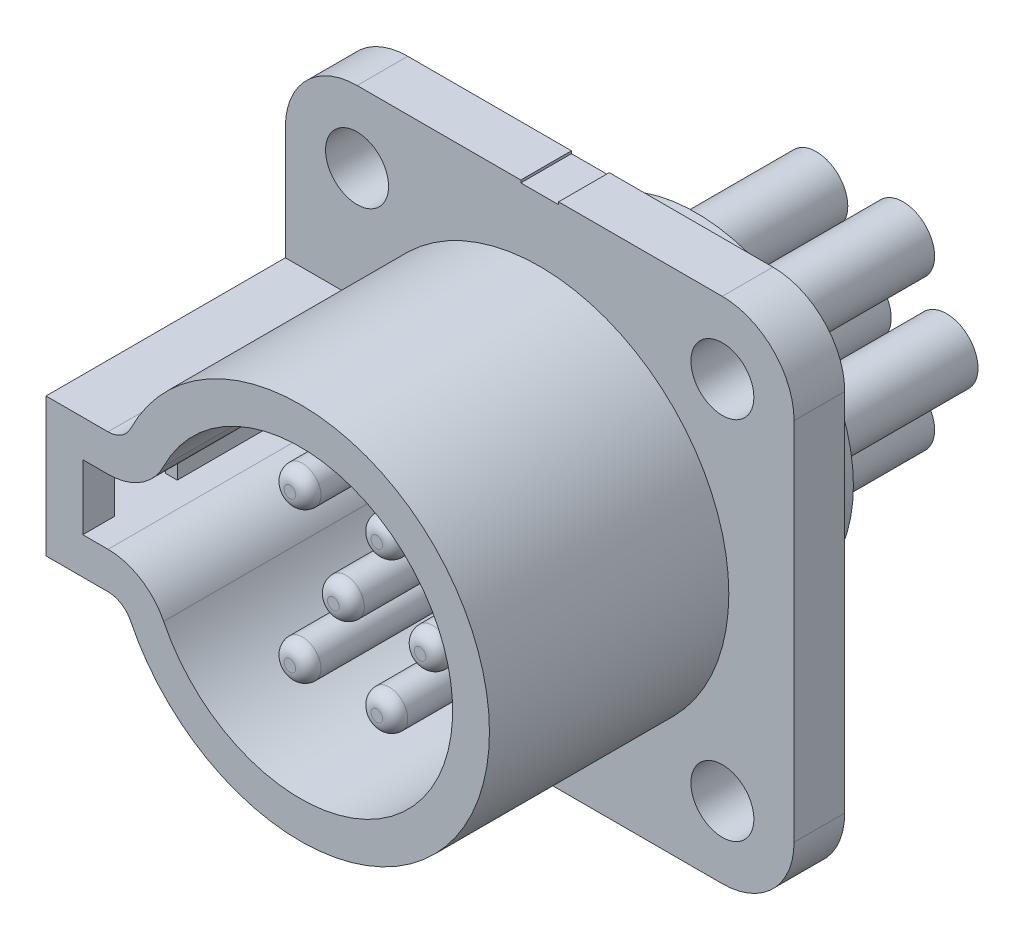
SolidWorks part; units mm, degrees
ref_plane "Front Plane" through (0, 0, 0) normal (0, 0, 1) x (1, 0, 0)
ref_plane "Top Plane" through (0, 0, 0) normal (0, 1, 0) x (1, 0, 0)
ref_plane "Right Plane" through (0, 0, 0) normal (1, 0, 0) x (0, 0, -1)
sketch "Sketch1" plane through (0, 0, 0) normal (0, 0, 1) x (1, 0, 0)
  line L1 (-10.095, 10.095) -> (10.095, 10.095)
  line L2 (-10.095, 10.095) -> (-10.095, -10.095)
  line L3 (-10.095, -10.095) -> (10.095, -10.095)
  line L4 (10.095, 10.095) -> (10.095, -10.095)
  line L5 (-10.095, 10.095) -> (10.095, -10.095) construction
  line L6 (-10.095, -10.095) -> (10.095, 10.095) construction
  point P0 (0, 0)
  dimension "D1" = 20.19
  dimension "D2" = 20.19
extrude "Boss-Extrude1" add sketch "Sketch1" along normal blind 2.01
sketch "Sketch2" plane through (0, 0, 2.01) normal (0, 0, 1) x (1, 0, 0)
  line L0 (0, 0) -> (0, 10.095) construction
  line L1 (10.095, 10.095) -> (-10.095, 10.095) construction
  line L2 (0, 0) -> (-10.095, 0) construction
  line L3 (-10.095, 10.095) -> (-10.095, -10.095) construction
  circle A0 centre (-7.25, 7.25) radius 1.25
  circle A1 centre (7.25, 7.25) radius 1.25
  circle A2 centre (7.25, -7.25) radius 1.25
  circle A3 centre (-7.25, -7.25) radius 1.25
  dimension "D1" = 2.5
  dimension "D2" = 7.25
  dimension "D3" = 7.25
extrude "Cut-Extrude1" cut sketch "Sketch2" against normal up to surface (2.01 mm away) up to face at (0, 0, 0)
fillet "Fillet1" radius 2.85 4 edges at (10.095, -10.095, 1.005) (-10.095, -10.095, 1.005) (10.095, 10.095, 1.005) (-10.095, 10.095, 1.005)
sketch "Sketch4" plane through (0, 0, 2.01) normal (0, 0, 1) x (1, 0, 0)
  line L0 (-10.095, -2.7495) -> (-10.095, 2.7495)
  line L1 (-10.095, 7.245) -> (-10.095, -7.245) construction
  line L2 (-10.095, 2.7495) -> (-7.6339, 2.7495)
  line L3 (-10.095, 0) -> (11.2357, 0) construction
  line L4 (-10.095, -2.7495) -> (-7.6339, -2.7495)
  line L5 (-8.635, -1.2895) -> (-8.635, 1.2895)
  line L6 (-8.635, 1.2895) -> (-7.6339, 1.2895)
  line L7 (-8.635, -1.2895) -> (-7.6339, -1.2895)
  line L8 (0, 10.095) -> (0, -11.6505) construction
  line L9 (7.245, 10.095) -> (-7.245, 10.095) construction
  line L10 (0, 6.045) -> (3.3385, 6.045) construction
  line L11 (0, -6.045) -> (3.3385, -6.045) construction
  line L12 (0, -7.505) -> (3.9298, -7.505) construction
  line L13 (0, 7.505) -> (4.2254, 7.505) construction
  arc A0 (-6.7363, 3.3086) -> (-6.7363, -3.3086) centre (0, 0) cw
  arc A1 (-6.7363, 3.3086) -> (-7.6339, 2.7495) centre (-7.6339, 3.7495) cw
  arc A2 (-6.7363, -3.3086) -> (-7.6339, -2.7495) centre (-7.6339, -3.7495) ccw
  arc A3 (-5.4259, 2.665) -> (-7.6339, 1.2895) centre (-7.6339, 3.7495) cw
  arc A4 (-5.4259, 2.665) -> (-5.4259, -2.665) centre (0, 0) cw
  arc A5 (-5.4259, -2.665) -> (-7.6339, -1.2895) centre (-7.6339, -3.7495) ccw
  dimension "D1" = 1
  dimension "D3" = 15.01
  dimension "D4" = 12.09
extrude "Boss-Extrude2" add sketch "Sketch4" along normal blind 9.5
sketch "Sketch5" plane through (-10.095, 0, 0) normal (-1, 0, 0) x (0, 0, 1)
  line L0 (0, 7.245) -> (0, -7.245) construction
  line L1 (0, 1.2895) -> (10.26, 1.2895)
  line L2 (0, 1.2895) -> (0, -1.2895)
  line L3 (0, -1.2895) -> (10.26, -1.2895)
  line L4 (10.26, 1.2895) -> (10.26, -1.2895)
  line L6 (0, 0) -> (-1.0293, 0) construction
  line L7 (11.51, 2.7495) -> (11.51, -2.7495) construction
  line L8 (11.51, 2.7495) -> (2.01, 2.7495) construction
  line L9 (11.51, -2.7495) -> (2.01, -2.7495) construction
  dimension "D1" = 1.25
  dimension "D2" = 1.46
  dimension "D3" = 1.46
extrude "Cut-Extrude2" cut sketch "Sketch5" against normal blind 1
sketch "Sketch6" plane through (-9.095, 0, 0) normal (-1, 0, 0) x (0, 0, 1)
  line L0 (0, -1.2895) -> (10.26, -1.2895) construction
  line L1 (10.26, 1.2895) -> (7.76, 1.2895)
  line L2 (10.26, 1.2895) -> (10.26, -1.2895)
  line L3 (10.26, -1.2895) -> (7.76, -1.2895)
  line L4 (7.76, 1.2895) -> (7.76, -1.2895)
  dimension "D1" = 2.5
extrude "Cut-Extrude3" cut sketch "Sketch6" against normal up to next
sketch "Sketch7" plane through (0, 0, 0) normal (0, 0, -1) x (-1, 0, 0)
  circle A0 centre (0, 0) radius 6.25
  dimension "D1" = 12.5
extrude "Boss-Extrude3" add sketch "Sketch7" along normal blind 4.19
sketch "Sketch8" plane through (0, 0, 2.01) normal (0, 0, 1) x (1, 0, 0)
  line L0 (-3.445, 0) -> (5.0962, 0) construction
  circle A0 centre (0, 0) radius 0.73
  circle A2 centre (3.445, 0) radius 0.73
  circle A3 centre (1.7225, 2.9835) radius 0.73
  circle A4 centre (-1.7225, 2.9835) radius 0.73
  circle A5 centre (1.7225, -2.9835) radius 0.73
  circle A6 centre (-1.7225, -2.9835) radius 0.73
  dimension "D1" = 1.46
extrude "Boss-Extrude4" add sketch "Sketch8" along normal blind 8.19 and the other way blind 7
fillet "Fillet2" radius 0.5 6 edges at (-2.4525, -2.9835, 10.2) (2.4525, 2.9835, 10.2) (0.9925, -2.9835, 10.2) (4.175, 0, 10.2) (0.73, 0, 10.2) (-0.9925, 2.9835, 10.2)
sketch "Sketch9" plane through (0, 0, -4.19) normal (0, 0, -1) x (-1, 0, 0)
  circle A0 centre (-1.7225, 2.9835) radius 1
  circle A1 centre (1.7225, 2.9835) radius 1
  circle A2 centre (0, 0) radius 1
  circle A3 centre (-3.445, 0) radius 1
  circle A4 centre (-1.7225, -2.9835) radius 1
  circle A5 centre (-1.7225, -2.9835) radius 1
  circle A6 centre (1.7225, -2.9835) radius 1
  point P0 (-1.7225, 2.9835)
  point P1 (1.7225, 2.9835)
  point P3 (-3.445, 0)
  point P5 (0, 0)
  point P7 (-1.7225, -2.9835)
  point P9 (1.7225, -2.9835)
  dimension "D1" = 2
  dimension "D2" = 2
  dimension "D3" = 2
  dimension "D4" = 2
  dimension "D5" = 2
  dimension "D6" = 2
extrude "Extrude-Thin1" add sketch "Sketch9" along normal blind 6.5 thin contours A0 | A1 | A2 | A3 | A4 | A6 thin type one direction wall 0.25
sketch "Sketch10" plane through (0, 10.095, 0) normal (0, 1, 0) x (1, 0, 0)
  line L0 (7.245, 0) -> (-7.245, 0) construction
  line L1 (-0.75, 0) -> (0.75, 0)
  line L2 (-0.75, 0) -> (-0.75, -2.01)
  line L3 (-0.75, -2.01) -> (0.75, -2.01)
  line L4 (0.75, 0) -> (0.75, -2.01)
  line L5 (7.245, -2.01) -> (-7.245, -2.01) construction
  line L6 (0, 4.99) -> (0, -4.274) construction
  line L7 (0.73, 4.99) -> (-0.73, 4.99) construction
  point P10 (0, -2.01)
  dimension "D1" = 1.5
  dimension "D2" = 0
extrude "Cut-Extrude4" cut sketch "Sketch10" against normal blind 0.1
equation "\"D2@Sketch1\"=\"D1@Sketch1\""
equation "\"D3@Sketch5\"=\"D2@Sketch5\""
equation "\"D2@Sketch9\"=\"D1@Sketch9\""
equation "\"D3@Sketch9\"=\"D1@Sketch9\""
equation "\"D4@Sketch9\"=\"D1@Sketch9\""
equation "\"D5@Sketch9\"=\"D1@Sketch9\""
equation "\"D6@Sketch9\"=\"D1@Sketch9\""
